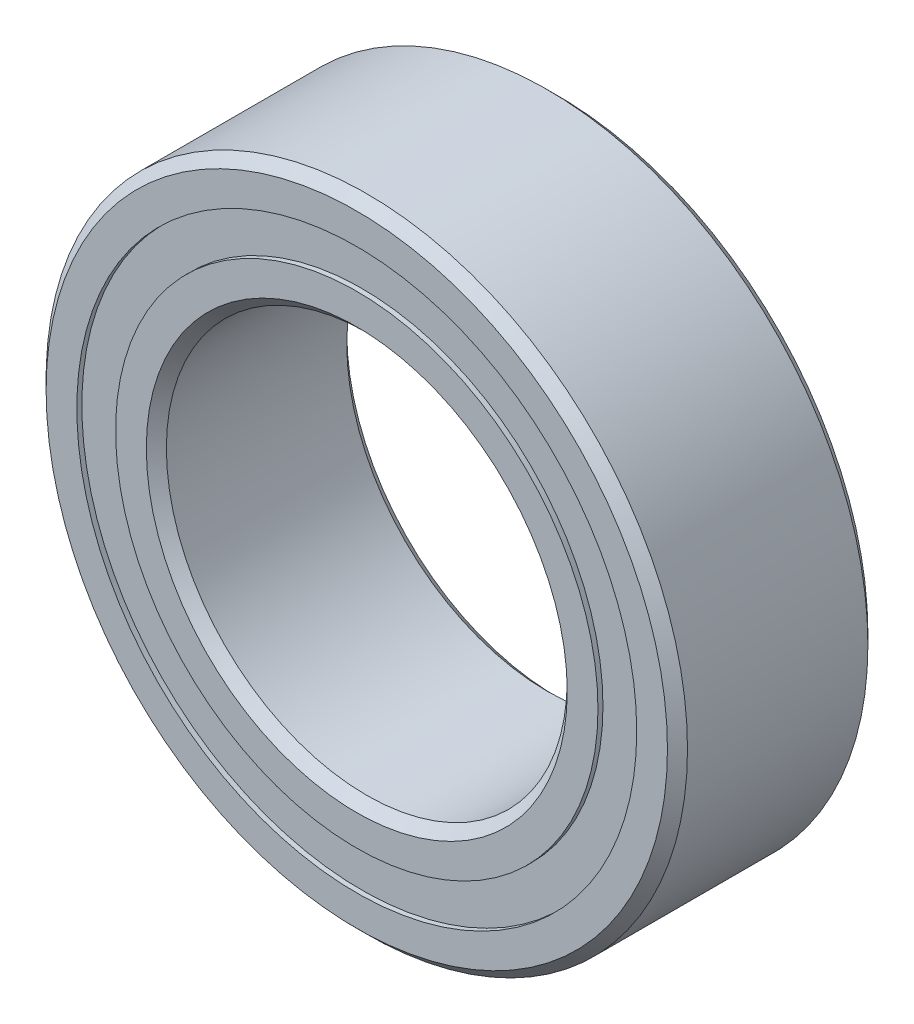
SolidWorks part; units mm, degrees
note: '?' marks a value the reader was unsure of.
material "Plain Carbon Steel"
ref_plane "Front Plane" through (0, 0, 0) normal (0, 0, 1) x (1, 0, 0)
ref_plane "Top Plane" through (0, 0, 0) normal (0, 1, 0) x (1, 0, 0)
ref_plane "Right Plane" through (0, 0, 0) normal (1, 0, 0) x (0, 0, -1)
sketch "Sketch1" plane through (0, 0, 0) normal (1, 0, 0) x (0, 0, -1)
  line L0 (-1.25, 0) -> (1.25, 0) construction
  line L1 (0, 4) -> (0, -4) construction
  line L2 (1.125, 4) -> (-1.125, 4)
  line L3 (-1.125, 4) -> (-1.25, 3.875)
  line L4 (-1.25, 3.875) -> (-1.25, 3.4918)
  line L5 (-1.25, 3.4918) -> (-0.5556, 3.4918)
  line L6 (1.25, 3.4918) -> (0.5556, 3.4918)
  line L7 (1.25, 3.875) -> (1.25, 3.4918)
  line L8 (1.125, 4) -> (1.25, 3.875)
  line L9 (0, 4) -> (0, 3.25) construction
  line L10 (0, 3.25) -> (0, 2.5) construction
  arc A0 (-0.5556, 3.4918) -> (0.5556, 3.4918) centre (0, 3.25) cw
  point P14 (0, 2.5)
  dimension "Width" = 2.5
  dimension "OD" = 8
  dimension "D1" = 45
  dimension "D2" = 0.125
  dimension "Shaft Dia" = 5
  dimension "D3" = 1.1111
  dimension "D4" = 0.2418
revolve "Revolve1" add sketch "Sketch1" angle 360 about L0
sketch "Sketch3" plane through (0, 0, 0) normal (1, 0, 0) x (0, 0, -1)
  line L0 (-1.25, 3.0082) -> (-0.5556, 3.0082)
  line L1 (0, 4) -> (0, -4) construction
  line L2 (-1.25, 3.875) -> (-1.25, 3.4918) construction
  line L3 (-1.25, 3.0082) -> (-1.25, 2.625)
  line L4 (-1.125, 4) -> (-1.25, 3.875) construction
  line L5 (-1.25, 2.625) -> (-1.125, 2.5)
  line L6 (-1.125, 2.5) -> (1.125, 2.5)
  line L7 (1.125, 4) -> (1.125, -4) construction
  line L8 (1.125, 2.5) -> (1.25, 2.625)
  line L9 (1.25, -3.875) -> (1.25, 3.875) construction
  line L10 (1.25, 2.625) -> (1.25, 3.0082)
  line L11 (1.25, 3.0082) -> (0.5556, 3.0082)
  line L13 (1.125, 4) -> (1.25, 3.875) construction
  arc A0 (0.5556, 3.4918) -> (-0.5556, 3.4918) centre (0, 3.25) ccw construction
  arc A1 (0.5556, 3.0082) -> (-0.5556, 3.0082) centre (0, 3.25) cw
revolve "Revolve3" add sketch "Sketch3" angle 360 about L0
sketch "Sketch4" plane through (0, 0, 0) normal (1, 0, 0) x (0, 0, -1)
  line L0 (-0.6059, 3.25) -> (0.6059, 3.25)
  arc A2 (-0.6059, 3.25) -> (0.6059, 3.25) centre (0, 3.25) cw
  arc A3 (0.5556, 3.4918) -> (-0.5556, 3.4918) centre (0, 3.25) ccw construction
revolve "Revolve4" add sketch "Sketch4" angle 360 about L0
ref_axis "Axis1" through (0, 0, -1.25) along (0, 0, 1)?
pattern_circular "CirPattern1" count 12 every 30 about axis through (0, 0, 0) along (0, 0, 1) of bodies 104
sketch "Sketch5" plane through (0, 0, 0) normal (1, 0, 0) x (0, 0, -1)
  line L0 (-1.25, 3.4918) -> (-0.5556, 3.4918) construction
  line L1 (-1.1875, 3.4918) -> (-0.6059, 3.4918)
  line L2 (-1.1875, 3.4918) -> (-1.1875, 3.0082)
  line L3 (-1.1875, 3.0082) -> (-0.6059, 3.0082)
  line L4 (-0.6059, 3.4918) -> (-0.6059, 3.0082)
  line L5 (-1.25, 3.0082) -> (-0.5556, 3.0082) construction
  line L6 (1.25, 3.4918) -> (0.5556, 3.4918) construction
  line L7 (1.1875, 3.4918) -> (0.6059, 3.4918)
  line L8 (1.1875, 3.4918) -> (1.1875, 3.0082)
  line L9 (1.1875, 3.0082) -> (0.6059, 3.0082)
  line L10 (0.6059, 3.4918) -> (0.6059, 3.0082)
  line L11 (1.25, 3.0082) -> (0.5556, 3.0082) construction
  line L12 (-1.125, 4) -> (-1.25, 3.875) construction
  point P18 (-1.1875, 3.9375)
revolve "Revolve5" add sketch "Sketch5" angle 360 about L0
sketch "Sketch6" plane through (0, 0, 0) normal (1, 0, 0) x (0, 0, -1)
  line L0 (1.25, 0) -> (-1.25, 0) construction
  line L1 (1.25, 3.4918) -> (0.4626, 3.4918)
  line L2 (1.25, 3.4918) -> (1.25, 6.9469)
  line L3 (1.25, 6.9469) -> (0.4626, 6.9469)
  line L4 (0.4626, 3.4918) -> (0.4626, 6.9469)
  dimension "Th" = 0.7874
  dimension "Flange OD" = 13.8938
revolve "Revolve6" [suppressed] add sketch "Sketch6" angle 360 about L0
equation "\"D2@Sketch1\" = \"Width@Sketch1\"*.05"
equation "\"D3@Sketch1\" = \"Width@Sketch1\"/2.25"
equation "\"D4@Sketch1\" = (((\"OD@Sketch1\"-\"Width@Sketch1\")/2)/3.25)/3.5"
equation "\"D2@CirPattern1\" = 360/\"Balls@CirPattern1\""
